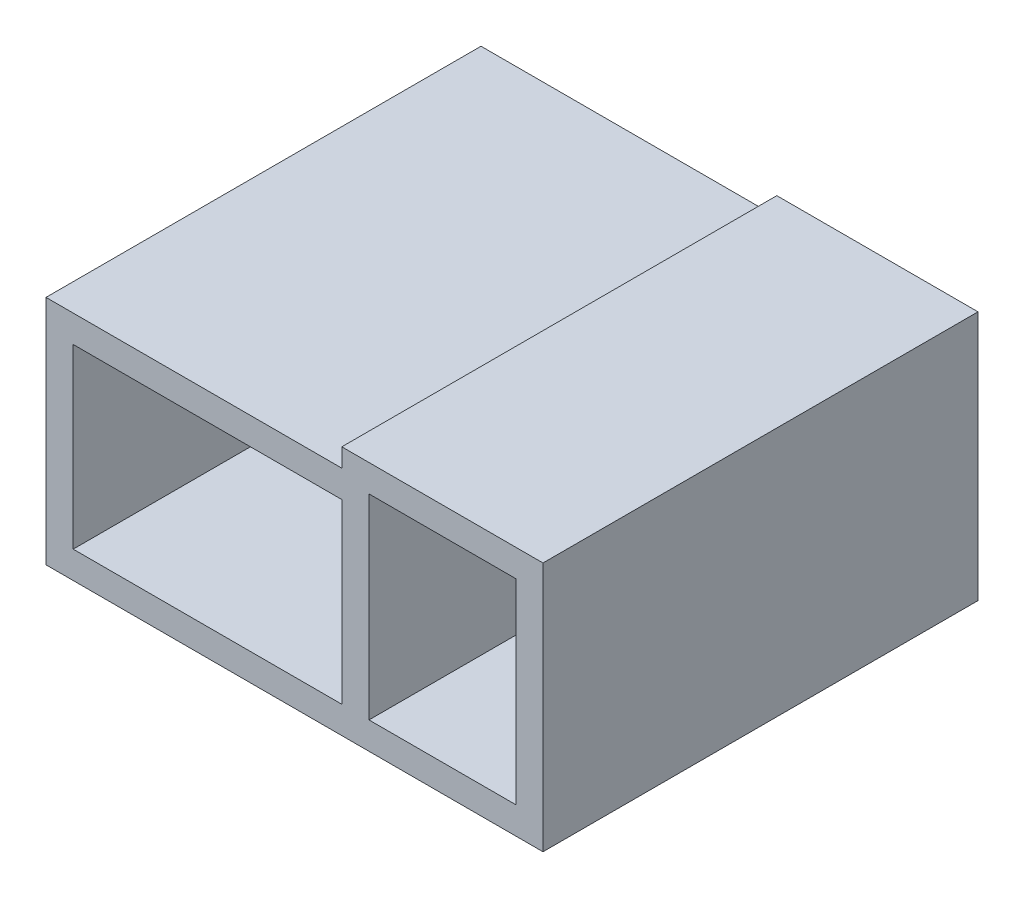
SolidWorks part; units mm, degrees
ref_plane "Front Plane" through (0, 0, 0) normal (0, 0, 1) x (1, 0, 0)
ref_plane "Top Plane" through (0, 0, 0) normal (0, 1, 0) x (1, 0, 0)
ref_plane "Right Plane" through (0, 0, 0) normal (1, 0, 0) x (0, 0, -1)
sketch "Sketch1" plane through (0, 0, 0) normal (0, 0, 1) x (1, 0, 0)
  line L0 (0, 0) -> (116.078, 0)
  line L1 (116.078, 0) -> (116.078, 58.42)
  line L2 (116.078, 58.42) -> (69.088, 58.42)
  line L3 (69.088, 58.42) -> (69.088, 54.102)
  line L4 (69.088, 54.102) -> (0, 54.102)
  line L5 (0, 54.102) -> (0, 0)
  line L6 (116.078, 0) -> (116.078, 6.35)
  line L13 (109.728, 52.07) -> (75.438, 52.07)
  line L14 (109.728, 52.07) -> (109.728, 6.35)
  line L15 (109.728, 6.35) -> (75.438, 6.35)
  line L16 (75.438, 6.35) -> (75.438, 52.07)
  line L17 (69.088, 47.752) -> (6.35, 47.752)
  line L18 (6.35, 47.752) -> (6.35, 6.35)
  line L19 (6.35, 6.35) -> (69.088, 6.35)
  line L20 (69.088, 6.35) -> (69.088, 47.752)
  dimension "D1" = 58.42
  dimension "D2" = 46.99
  dimension "D3" = 69.088
  dimension "D4" = 54.102
  dimension "D5" = 6.35
  dimension "D8" = 6.35
  dimension "D11" = 6.35
extrude "Boss-Extrude1" add sketch "Sketch1" along normal blind 101.6 contours L4 L5 L0 L1 L2 L3 L20 L19 L18 L17 L15 L16 L13 L14 region at (1.2995, 27.051, 0)
